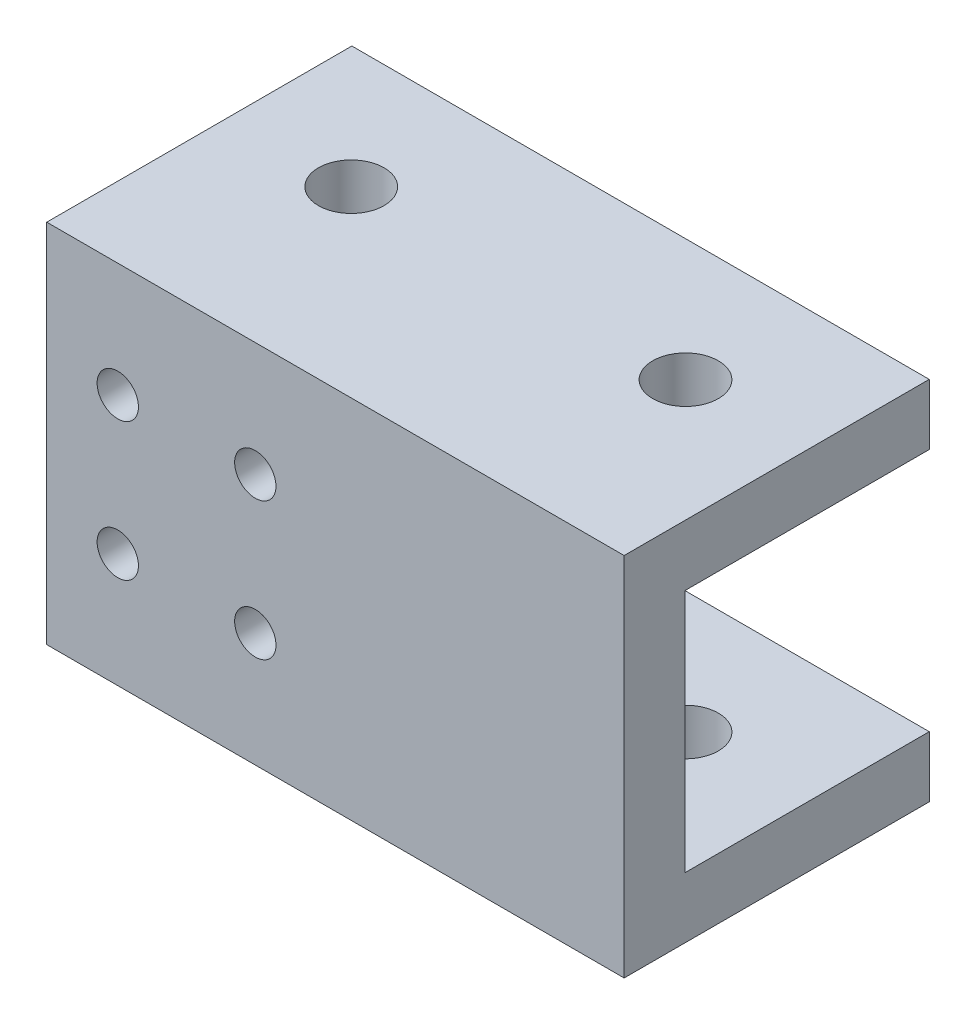
SolidWorks part; units mm, degrees
ref_plane "Front Plane" through (0, 0, 0) normal (0, 0, 1) x (1, 0, 0)
ref_plane "Top Plane" through (0, 0, 0) normal (0, 1, 0) x (1, 0, 0)
ref_plane "Right Plane" through (0, 0, 0) normal (1, 0, 0) x (0, 0, -1)
sketch "Sketch1" plane through (0, 0, 0) normal (1, 0, 0) x (0, 0, -1)
  line L0 (10.05, -10.05) -> (10.05, -15.05)
  line L1 (10.05, -10.05) -> (-10.05, -10.05) construction
  line L2 (10.05, -10.05) -> (10.05, 10.05) construction
  line L3 (10.05, 10.05) -> (-10.05, 10.05) construction
  line L4 (-10.05, -10.05) -> (-10.05, 10.05) construction
  line L5 (10.05, -10.05) -> (-10.05, 10.05) construction
  line L6 (10.05, 10.05) -> (-10.05, -10.05) construction
  line L7 (10.05, -15.05) -> (-15.05, -15.05) construction
  line L8 (10.05, -15.05) -> (10.05, 15.05) construction
  line L9 (10.05, 15.05) -> (-15.05, 15.05) construction
  line L10 (-15.05, -15.05) -> (-15.05, 15.05) construction
  line L11 (10.05, -15.05) -> (-15.05, 15.05) construction
  line L12 (10.05, 15.05) -> (-15.05, -15.05) construction
  line L13 (10.05, -15.05) -> (-15.05, -15.05)
  line L14 (-15.05, -15.05) -> (-15.05, 15.05)
  line L15 (-15.05, 15.05) -> (10.05, 15.05)
  line L16 (10.05, 15.05) -> (10.05, 10.05)
  line L17 (10.05, 10.05) -> (-10.05, 10.05)
  line L18 (-10.05, 10.05) -> (-10.05, -10.05)
  line L19 (-10.05, -10.05) -> (10.05, -10.05)
  line L20 (-10.05, 10.05) -> (-15.05, 10.05) construction
  point P0 (0, 0)
  point P6 (-2.5, 0)
  point P11 (-14.7712, 14.7712)
  dimension "D1" = 20.1
  dimension "D2" = 5
extrude "Boss-Extrude1" add sketch "Sketch1" along normal blind 47.5
sketch "Sketch2" plane through (0, 0, 10.05) normal (0, 0, -1) x (-1, 0, 0)
  line L0 (0, -10.05) -> (0, 10.05) construction
  line L1 (-11.5, 0) -> (-11.5, 10.05) construction
  line L2 (-47.5, 10.05) -> (0, 10.05) construction
  line L3 (-17.1569, 5.6569) -> (-11.5, 0) construction
  circle A0 centre (-11.5, 0) radius 11.5 construction
  circle A1 centre (-17.1569, 5.6569) radius 1.5
  circle A2 centre (-5.8431, 5.6569) radius 1.5
  circle A3 centre (-5.8431, -5.6569) radius 1.5
  circle A4 centre (-17.1569, -5.6569) radius 1.5
  point P16 (-11.5, 0)
  dimension "D1" = 23
  dimension "D2" = 3
  dimension "D3" = 8
  dimension "D5" = 45
  dimension "D4" = 4
hole_wizard "CSK for M3 Flat Head Machine Screw1" positions "Sketch3" profile "Sketch4" countersink size "M3" standard "ANSI Metric" end condition through all
sketch "Sketch3" plane through (0, 0, 10.05) normal (0, 0, -1) x (-1, 0, 0)
  point P0 (-17.1569, 5.6569)
  point P3 (-5.8431, 5.6569)
  point P6 (-5.8431, -5.6569)
  point P9 (-17.1569, -5.6569)
sketch "Sketch4" plane through (17.1569, 5.6569, 10.05) normal (1, 0, 0) x (0, 1, 0)
  line L0 (0, 0) -> (0, 5)
  line L1 (0, 5) -> (1.7, 5)
  line L2 (1.7, 5) -> (1.7, 1.45)
  line L3 (1.7, 1.45) -> (3.15, 0)
  line L5 (3.15, 0) -> (0, 0)
  line L6 (-1.7, 1.45) -> (-3.15, 0) construction
  line L11 (0, -6.35) -> (0, 107.95) construction
  dimension "Thru Hole Dia." = 3.4
  dimension "Thru Hole Depth" = 5
  dimension "Near C'Sink Dia." = 6.3
  dimension "Near C'Sink Angle" = 90
sketch "Sketch5" plane through (0, 15.05, 0) normal (0, 1, 0) x (1, 0, 0)
  line L0 (0, 0) -> (47.5, 0) construction
  line L1 (47.5, 10.05) -> (47.5, -15.05) construction
  line L2 (0, 10.05) -> (0, -15.05) construction
  circle A0 centre (10, 0) radius 2.7
  circle A1 centre (37.5, 0) radius 2.7
  dimension "D1" = 5.4
  dimension "D2" = 10
  dimension "D3" = 10
extrude "Cut-Extrude1" cut sketch "Sketch5" against normal through all
